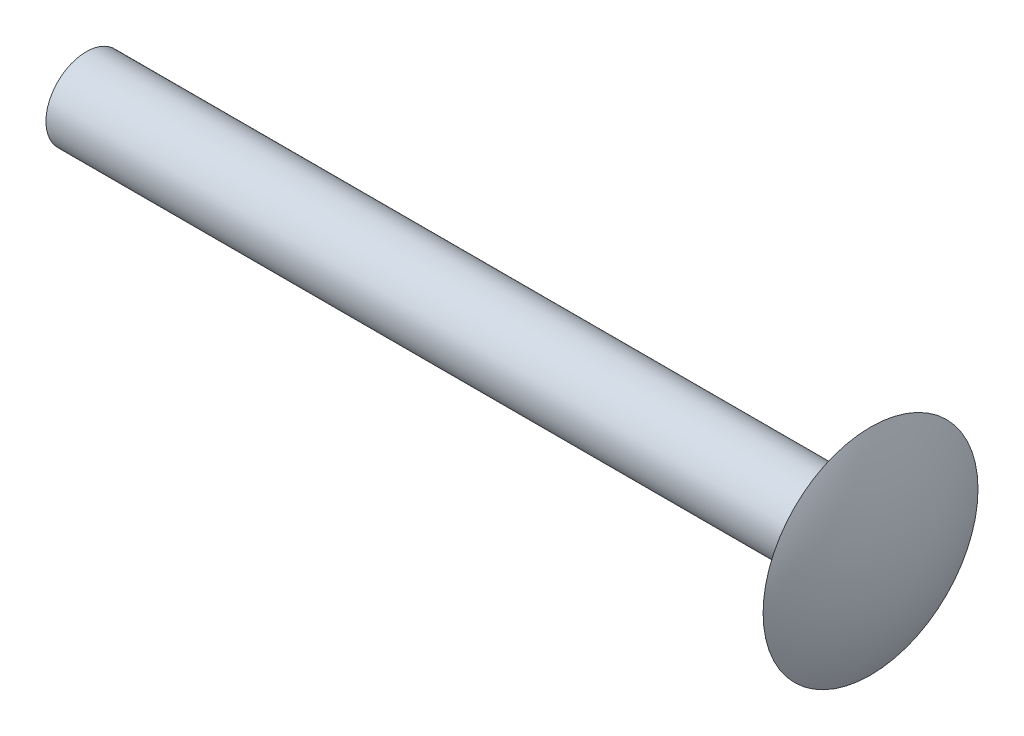
SolidWorks part; units mm, degrees
ref_plane "Front Plane" through (0, 0, 0) normal (0, 0, 1) x (1, 0, 0)
ref_plane "Top Plane" through (0, 0, 0) normal (0, 1, 0) x (1, 0, 0)
ref_plane "Right Plane" through (0, 0, 0) normal (1, 0, 0) x (0, 0, -1)
sketch "Shaft Sketch" plane through (0, 0, 0) normal (1, 0, 0) x (0, 0, -1)
  circle A0 centre (0, 0) radius 7.5
  point P2 (0, 0)
  point P4 (0, 0)
  dimension "D1" = 15
extrude "Shaft Extrude" add sketch "Shaft Sketch" along normal blind 146
sketch "Head Sketch" plane through (0, 0, 0) normal (0, 0, 1) x (1, 0, 0)
  line L0 (151, 0) -> (146, 0)
  line L1 (146, 0) -> (146, 20)
  line L2 (146, -7.5) -> (146, 7.5) construction
  arc A0 (151, 0) -> (146, 20) centre (108.5, 0) ccw
  point P5 (0, 0)
  point P6 (136.8058, 29.4368)
  point P7 (0, 0)
  point P8 (0, 0)
  point P11 (0, 0)
  point P13 (0, 0)
  point P14 (0, 0)
  point P15 (130.0379, 0)
  point P16 (0, 0)
  dimension "D1" = 20
  dimension "D2" = 5
revolve "Head Revolution" add sketch "Head Sketch" angle 360 about L0
